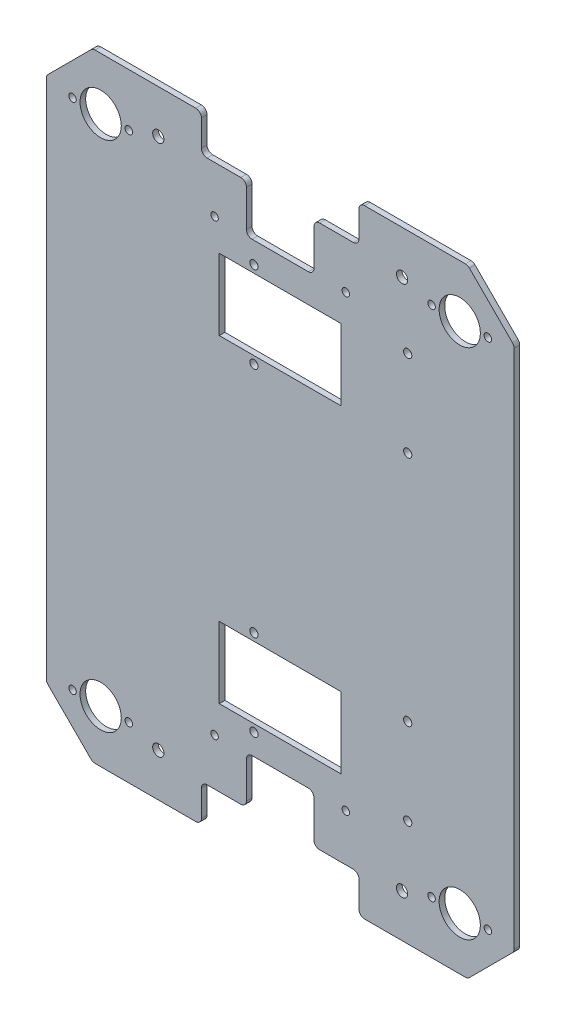
SolidWorks part; units mm, degrees
material "Alliage 1060"
ref_plane "Plan de dessus" through (0, 0, 0) normal (0, 0, 1) x (1, 0, 0)
ref_plane "Plan de droite" through (0, 0, 0) normal (0, 1, 0) x (1, 0, 0)
ref_plane "Plan de face" through (0, 0, 0) normal (1, 0, 0) x (0, 0, -1)
sketch "Esquisse1" plane through (0, 0, 0) normal (0, 0, 1) x (1, 0, 0)
  line L0 (0, 0) -> (-200, 0)
  line L1 (-200, 0) -> (-224.7487, 24.7487)
  line L2 (-224.7487, 24.7487) -> (-224.7487, 304.7487)
  line L3 (-224.7487, 304.7487) -> (-200, 329.4975)
  line L4 (-200, 329.4975) -> (0, 329.4975)
  line L5 (0, 329.4975) -> (24.7487, 304.7487)
  line L6 (24.7487, 304.7487) -> (24.7487, 24.7487)
  line L7 (24.7487, 24.7487) -> (0, 0)
  dimension "D1" = 280
  dimension "D2" = 35
  dimension "D3" = 135
  dimension "D4" = 200
extrude "Base" add sketch "Esquisse1" along normal blind 3
sketch "Esquisse3" plane through (0, 0, 0) normal (0, 0, -1) x (-1, 0, 0)
  line L0 (142, 0) -> (142, 20)
  line L1 (200, 0) -> (0, 0) construction
  line L2 (142, 20) -> (118, 20)
  line L3 (118, 20) -> (118, 45.5)
  line L4 (118, 45.5) -> (82, 45.5)
  line L5 (82, 45.5) -> (82, 20)
  line L6 (82, 20) -> (58, 20)
  line L7 (58, 20) -> (58, 0)
  line L8 (-24.7487, 164.7487) -> (224.7487, 164.7487) construction
  line L9 (-24.7487, 24.7487) -> (-24.7487, 304.7487) construction
  line L10 (224.7487, 304.7487) -> (224.7487, 24.7487) construction
  line L11 (58, 0) -> (142, 0)
  line L12 (58, 329.4975) -> (142, 329.4975)
  line L13 (142, 329.4975) -> (142, 309.4975)
  line L14 (142, 309.4975) -> (118, 309.4975)
  line L15 (118, 309.4975) -> (118, 283.9975)
  line L16 (118, 283.9975) -> (82, 283.9975)
  line L17 (82, 283.9975) -> (82, 309.4975)
  line L18 (82, 309.4975) -> (58, 309.4975)
  line L19 (58, 309.4975) -> (58, 329.4975)
  line L20 (100, 45.5) -> (100, -49954.5) construction
  line L22 (67.5, 266.7487) -> (132.5, 266.7487)
  line L23 (67.5, 266.7487) -> (67.5, 236.7487)
  line L24 (67.5, 236.7487) -> (132.5, 236.7487)
  line L25 (132.5, 266.7487) -> (132.5, 236.7487)
  line L26 (132.5, 62.7487) -> (132.5, 92.7487)
  line L27 (67.5, 92.7487) -> (132.5, 92.7487)
  line L28 (67.5, 62.7487) -> (132.5, 62.7487)
  line L29 (67.5, 62.7487) -> (67.5, 92.7487)
  circle A0 centre (65, 45) radius 2
  circle A1 centre (135, 45) radius 2
  circle A2 centre (135, 284.4975) radius 2
  circle A3 centre (65, 284.4975) radius 2
  point P4 (100, 45.5)
  point P11 (100, 0)
  point P40 (100, 266.7487)
  point P41 (132.5, 251.7487)
  dimension "D7" = 4
  dimension "D5" = 25
  dimension "D1" = 20
  dimension "D2" = 24
  dimension "D3" = 36
  dimension "D4" = 25.5
  dimension "D6" = 7
  dimension "D8" = 87
  dimension "D9" = 30
  dimension "D10" = 65
extrude "Perçage roues encodeuses" cut sketch "Esquisse3" against normal through all
fillet "Congé1" radius 3 24 edges at (-224.7487, 24.7487, 1.5) (24.7487, 24.7487, 1.5) (0, 0, 1.5) (-142, 20, 1.5) (-118, 45.5, 1.5) (-118, 20, 1.5) (-200, 0, 1.5) (-142, 0, 1.5) (-82, 45.5, 1.5) (-58, 20, 1.5) (-82, 20, 1.5) (-58, 0, 1.5) (24.7487, 304.7487, 1.5) (-142, 309.4975, 1.5) (-118, 283.9975, 1.5) (-224.7487, 304.7487, 1.5) (-200, 329.4975, 1.5) (-142, 329.4975, 1.5) (-118, 309.4975, 1.5) (-82, 283.9975, 1.5) (-58, 309.4975, 1.5) (-82, 309.4975, 1.5) (-58, 329.4975, 1.5) (0, 329.4975, 1.5)
sketch "Esquisse6" plane through (0, 0, 3) normal (0, 0, 1) x (1, 0, 0)
  line L0 (-195.7487, 28) -> (-210.7487, 28) construction
  line L1 (-195.7487, 28) -> (-180.7487, 28) construction
  line L2 (-100, 231.5685) -> (-100, -49768.4315) construction
  line L4 (-67.5, 236.7487) -> (-132.5, 236.7487) construction
  line L5 (-203.2843, 164.7487) -> (49796.7157, 164.7487) construction
  line L6 (-224.7487, 303.5061) -> (-224.7487, 25.9914) construction
  line L15 (-198.7574, 0) -> (-145, 0) construction
  circle A25 centre (-180.7487, 28) radius 2
  circle A26 centre (-210.7487, 28) radius 2
  circle A27 centre (-195.7487, 28) radius 11
  circle A31 centre (-19.2513, 28) radius 2
  circle A32 centre (10.7487, 28) radius 2
  circle A33 centre (-4.2513, 28) radius 11
  circle A34 centre (-4.2513, 301.4975) radius 11
  circle A35 centre (10.7487, 301.4975) radius 2
  circle A36 centre (-19.2513, 301.4975) radius 2
  circle A37 centre (-195.7487, 301.4975) radius 11
  circle A38 centre (-210.7487, 301.4975) radius 2
  circle A39 centre (-180.7487, 301.4975) radius 2
  point P15 (-100, 236.7487)
  point P20 (-224.7487, 164.7487)
  dimension "D2" = 4
  dimension "D3" = 15
  dimension "D4" = 15
  dimension "D5" = 180
  dimension "D9" = 29
  dimension "D13" = 22
  dimension "D15" = 28
extrude "Perçage billes porteuses" cut sketch "Esquisse6" against normal up to next
sketch "Esquisse8" plane through (0, 0, 3) normal (0, 0, 1) x (1, 0, 0)
  line L0 (-100, 283.9975) -> (-100, 92.7487) construction
  line L1 (-85, 283.9975) -> (-115, 283.9975) construction
  line L2 (-132.5, 92.7487) -> (-67.5, 92.7487) construction
  line L3 (-145, 329.4975) -> (-198.7574, 329.4975) construction
  line L4 (-142, 312.4975) -> (-142, 326.4975) construction
  line L5 (-198.7574, 0) -> (-145, 0) construction
  line L6 (-142, 3) -> (-142, 17) construction
  circle A0 centre (-165, 23) radius 3
  circle A1 centre (-165, 306.4975) radius 3
  circle A2 centre (-35, 306.4975) radius 3
  circle A3 centre (-35, 23) radius 3
  dimension "D1" = 23
  dimension "D2" = 23
  dimension "D3" = 6
  dimension "D4" = 23
  dimension "D5" = 23
  dimension "D6" = 6
extrude "Perçage profilés" cut sketch "Esquisse8" against normal up to next
sketch "Esquisse10" plane through (0, 0, 3) normal (0, 0, 1) x (1, 0, 0)
  line L0 (-224.7487, 303.5061) -> (-224.7487, 25.9914) construction
  line L1 (-100, 236.7487) -> (-100, 92.7487) construction
  line L2 (-123.75, 201.9487) -> (-100, 201.9487) construction
  line L3 (-67.5, 236.7487) -> (-132.5, 236.7487) construction
  line L4 (-100, 201.9487) -> (21.8665, 201.9487) construction
  line L5 (-224.7487, 164.7487) -> (24.7487, 164.7487) construction
  line L6 (24.7487, 25.9914) -> (24.7487, 303.5061) construction
  line L7 (-132.5, 92.7487) -> (-67.5, 92.7487) construction
  line L8 (-158.75, 201.9487) -> (-123.75, 201.9487) construction
  line L9 (-132.5, 251.7487) -> (-67.5, 251.7487) construction
  line L10 (-132.5, 236.7487) -> (-132.5, 266.7487) construction
  line L11 (-67.5, 266.7487) -> (-67.5, 236.7487) construction
  line L12 (-100, 127.5487) -> (-139.6239, 127.5487) construction
  line L13 (-100, 127.5487) -> (10.2968, 127.5487) construction
  circle A8 centre (-123.75, 201.9487) radius 1.75
  circle A9 centre (-120, 230.7487) radius 1.75
  circle A10 centre (-158.75, 201.9487) radius 1.75
  circle A11 centre (-80, 230.7487) radius 1.75
  circle A18 centre (-80, 98.7487) radius 1.75
  circle A19 centre (-120, 98.7487) radius 1.75
  circle A20 centre (-71.75, 201.9487) radius 1.75
  circle A21 centre (-40.75, 201.9487) radius 1.75
  circle A22 centre (-128.25, 127.5487) radius 1.75
  circle A23 centre (-159.25, 127.5487) radius 1.75
  circle A24 centre (-76.25, 127.5487) radius 1.75
  circle A25 centre (-41.25, 127.5487) radius 1.75
  dimension "D1" = 3.5
  dimension "D2" = 23.75
  dimension "D3" = 20
  dimension "D4" = 3.5
  dimension "D5" = 3.5
  dimension "D6" = 35
  dimension "D7" = 21
  dimension "D8" = 28.8
  dimension "D9" = 3.5
  dimension "D10" = 3.5
  dimension "D12" = 31
  dimension "D13" = 28.8
  dimension "D14" = 3.5
  dimension "D15" = 3.5
  dimension "D16" = 3.5
  dimension "D17" = 3.5
  dimension "D18" = 28.25
  dimension "D19" = 31
  dimension "D21" = 35
  dimension "D11" = 28.25
  dimension "D20" = 23.75
sketch "Esquisse15" plane through (0, 0, 0) normal (0, 0, -1) x (-1, 0, 0)
  line L0 (114, 102.7487) -> (32, 102.7487) construction
  line L1 (-24.7487, 164.7487) -> (23.202, 164.7487) construction
  line L2 (-24.7487, 25.9914) -> (-24.7487, 303.5061) construction
  line L3 (100, 92.7487) -> (100, 134.4542) construction
  line L4 (132.5, 92.7487) -> (67.5, 92.7487) construction
  line L5 (0, 79.7487) -> (59.1109, 79.7487) construction
  circle A0 centre (114, 102.7487) radius 2.2
  circle A1 centre (32, 102.7487) radius 2.2
  circle A2 centre (114, 56.7487) radius 2.2
  circle A3 centre (32, 56.7487) radius 2.2
  circle A4 centre (32, 272.7487) radius 2.2
  circle A5 centre (114, 272.7487) radius 2.2
  circle A6 centre (114, 226.7487) radius 2.2
  circle A7 centre (32, 226.7487) radius 2.2
  dimension "D2" = 4.4
  dimension "D1" = 82
  dimension "D3" = 85
  dimension "D4" = 23
  dimension "D5" = 14
extrude "Perçage bloc moteur" cut sketch "Esquisse15" against normal up to surface (3 mm away) up to face at (-38, 23, 3)
sketch "Esquisse16" plane through (0, 0, 0) normal (0, 0, -1) x (-1, 0, 0)
  line L0 (224.7487, 164.7487) -> (-24.7487, 164.7487) construction
  line L1 (67.5, 60.7487) -> (132.5, 60.7487)
  line L2 (67.5, 60.7487) -> (67.5, 98.7487)
  line L3 (67.5, 98.7487) -> (132.5, 98.7487)
  line L4 (132.5, 60.7487) -> (132.5, 98.7487)
  line L5 (224.7487, 303.5061) -> (224.7487, 25.9914) construction
  line L6 (-24.7487, 25.9914) -> (-24.7487, 303.5061) construction
  line L7 (100, 329.4975) -> (100, 0) construction
  line L8 (100, 0) -> (55, 0) construction
  line L9 (67.5, 230.7487) -> (132.5, 230.7487)
  line L10 (132.5, 268.7487) -> (132.5, 230.7487)
  line L11 (67.5, 268.7487) -> (132.5, 268.7487)
  line L12 (67.5, 268.7487) -> (67.5, 230.7487)
  point P10 (132.5, 79.7487)
  point P13 (100, 164.7487)
  point P16 (100, 60.7487)
  dimension "D1" = 85
  dimension "D2" = 38
  dimension "D3" = 65
extrude "Enlèv. mat.-Extru.1" cut sketch "Esquisse16" against normal through all
sketch "Esquisse14" plane through (0, 329.4975, 0) normal (0, 1, 0) x (1, 0, 0)
  line L0 (-100, -3) -> (-100, 0) construction
  line L1 (-85, -3) -> (-115, -3) construction
  line L2 (-85, 0) -> (-115, 0) construction
